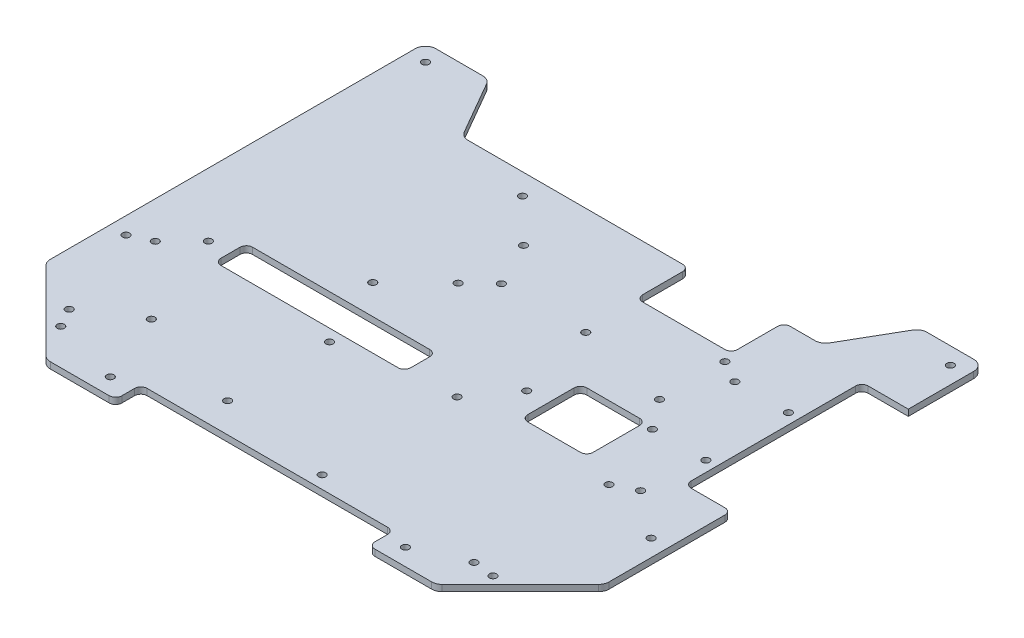
SolidWorks part; units mm, degrees
material "Acier non allié"
ref_plane "Front" through (0, 0, 0) normal (0, 0, 1) x (1, 0, 0)
ref_plane "Top" through (0, 0, 0) normal (0, 1, 0) x (1, 0, 0)
ref_plane "Right" through (0, 0, 0) normal (1, 0, 0) x (0, 0, -1)
sketch "Esquisse1" plane through (0, 0, 0) normal (0, 1, 0) x (1, 0, 0)
  line L0 (0, 0) -> (0, 190) construction
  line L1 (-92.5, 0) -> (92.5, 0)
  line L2 (92.5, 0) -> (132.5, 40)
  line L3 (132.5, 40) -> (132.5, 220)
  line L4 (132.5, 220) -> (102.5, 220)
  line L5 (102.5, 220) -> (85.1795, 190)
  line L6 (85.1795, 190) -> (-85.1795, 190)
  line L7 (-102.5, 220) -> (-85.1795, 190)
  line L8 (-132.5, 220) -> (-102.5, 220)
  line L9 (-132.5, 40) -> (-132.5, 220)
  line L10 (-92.5, 0) -> (-132.5, 40)
  dimension "D1" = 132.5
  dimension "D2" = 220
  dimension "D3" = 60
  dimension "D4" = 30
  dimension "D5" = 40
  dimension "D6" = 40
  dimension "D7" = 30
extrude "Boss.-Extru.1" add sketch "Esquisse1" along normal blind 3
fillet "Congé1" radius 5 10 edges at (92.5, 1.5, 0) (132.5, 1.5, -40) (132.5, 1.5, -220) (102.5, 1.5, -220) (85.1795, 1.5, -190) (-85.1795, 1.5, -190) (-102.5, 1.5, -220) (-132.5, 1.5, -220) (-92.5, 1.5, 0) (-132.5, 1.5, -40)
sketch "Esquisse2" plane through (0, 3, 0) normal (0, 1, 0) x (1, 0, 0)
  line L0 (0, 0) -> (0, 294.1173) construction
  line L2 (-90.4289, 0) -> (90.4289, 0) construction
  circle A0 centre (70, 8) radius 1
  circle A1 centre (124.5, 70) radius 1
  circle A2 centre (124.5, 212) radius 1
  circle A3 centre (-124.5, 212) radius 1
  circle A4 centre (-124.5, 70) radius 1
  circle A5 centre (-70, 8) radius 1
  dimension "D2" = 2
  dimension "D6" = 2
  dimension "D9" = 2
  dimension "D1" = 70
  dimension "D3" = 8
  dimension "D4" = 124.5
  dimension "D5" = 70
  dimension "D7" = 124.5
  dimension "D8" = 212
extrude "Enlèv. mat.-Extru.1" cut sketch "Esquisse2" against normal blind 3
hole_wizard "Dégagement M31" positions "Esquisse3" profile "Esquisse4" hole size "M3" standard "ISO" end condition through all
sketch "Esquisse3" plane through (0, 3, 0) normal (0, 1, 0) x (1, 0, 0)
  point P0 (70, 8)
  point P3 (-70, 8)
  point P6 (-124.5, 70)
  point P9 (-124.5, 212)
  point P12 (124.5, 212)
  point P15 (124.5, 70)
sketch "Esquisse4" plane through (70, 3, -8) normal (1, 0, 0) x (0, 0, 1)
  line L0 (0, 0) -> (0, 3)
  line L1 (0, 3) -> (1.7, 3)
  line L2 (1.7, 3) -> (1.7, 0)
  line L5 (1.7, 0) -> (0, 0)
  line L11 (0, -6.35) -> (0, 107.95) construction
  dimension "Diamètre du perçage jusqu'au prochain" = 3.4
  dimension "Profondeur du perçage jusqu'au prochain" = 3
sketch "Esquisse5" plane through (0, 3, 0) normal (0, 1, 0) x (1, 0, 0)
  line L0 (82.2927, 190) -> (-82.2927, 190) construction
  line L1 (67.5, 190) -> (22.5, 190)
  line L2 (67.5, 190) -> (67.5, 165)
  line L3 (67.5, 165) -> (22.5, 165)
  line L4 (22.5, 190) -> (22.5, 165)
  line L5 (132.5, 42.0711) -> (132.5, 215) construction
  line L6 (132.5, 184) -> (110.5, 184)
  line L7 (132.5, 184) -> (132.5, 100)
  line L8 (132.5, 100) -> (110.5, 100)
  line L9 (110.5, 184) -> (110.5, 100)
  line L10 (127.5, 220) -> (105.3868, 220) construction
  dimension "D1" = 25
  dimension "D2" = 65
  dimension "D3" = 110
  dimension "D4" = 36
  dimension "D5" = 120
  dimension "D6" = 22
extrude "Enlèv. mat.-Extru.2" cut sketch "Esquisse5" against normal through all
fillet "Congé2" radius 3 7 edges at (132.5, 1.5, -100) (110.5, 1.5, -100) (110.5, 1.5, -184) (67.5, 1.5, -190) (67.5, 1.5, -165) (22.5, 1.5, -165) (22.5, 1.5, -190)
sketch "Esquisse6" plane through (0, 3, 0) normal (0, 1, 0) x (1, 0, 0)
  line L0 (110.5, 144.5) -> (-167.6757, 144.5) construction
  line L1 (110.5, 181) -> (110.5, 103) construction
  line L2 (-90.4289, 0) -> (90.4289, 0) construction
  line L3 (110.5, 181) -> (110.5, 103) construction
  circle A0 centre (69.5, 160) radius 1
  circle A1 centre (-26, 160) radius 1
  circle A2 centre (-46.5, 180) radius 1
  circle A3 centre (69.5, 129) radius 1
  circle A4 centre (-26, 129) radius 1
  circle A5 centre (-46.5, 109) radius 1
  dimension "D4" = 2
  dimension "D6" = 2
  dimension "D10" = 2
  dimension "D1" = 144.5
  dimension "D2" = 41
  dimension "D3" = 15.5
  dimension "D5" = 136.5
  dimension "D7" = 15.5
  dimension "D8" = 35.5
  dimension "D9" = 157
extrude "Enlèv. mat.-Extru.3" cut sketch "Esquisse6" against normal through all
hole_wizard "Dégagement M32" positions "Esquisse7" profile "Esquisse8" hole size "M3" standard "ISO"
sketch "Esquisse7" plane through (0, 3, 0) normal (0, 1, 0) x (1, 0, 0)
  point P0 (-46.5, 109)
  point P3 (-26, 129)
  point P6 (-26, 160)
  point P9 (-46.5, 180)
  point P12 (69.5, 160)
  point P15 (69.5, 129)
sketch "Esquisse8" plane through (-46.5, 3, -109) normal (1, 0, 0) x (0, 0, 1)
  line L0 (0, 0) -> (0, 11.0215)
  line L1 (0, 11.0215) -> (1.7, 10)
  line L2 (1.7, 10) -> (1.7, 0)
  line L5 (1.7, 0) -> (0, 0)
  line L10 (0, 11.0215) -> (-1.7, 10) construction
  line L11 (0, -6.35) -> (0, 107.95) construction
  dimension "Diamètre du perçage" = 3.4
  dimension "Profondeur du perçage" = 10
  dimension "Angle de pointe" = 118
sketch "Esquisse9" plane through (0, 3, 0) normal (0, 1, 0) x (1, 0, 0)
  line L0 (132.5, 42.0711) -> (132.5, 97) construction
  line L1 (-90.4289, 0) -> (90.4289, 0) construction
  line L2 (-107.5, 26) -> (-32.37, 26) construction
  line L7 (20.5, 18) -> (20.5, 82) construction
  line L8 (25.5, 165) -> (64.5, 165) construction
  line L9 (24.5, 139) -> (-15.5, 139) construction
  line L10 (110.5, 181) -> (110.5, 103) construction
  line L12 (127.5, 220) -> (105.3868, 220) construction
  line L13 (-32.37, 26) -> (-32.37, 74.3362) construction
  line L14 (-32.37, 74.3362) -> (-115, 74.3362) construction
  line L15 (-132.5, 215) -> (-132.5, 42.0711) construction
  circle A0 centre (105.5, 115) radius 1
  circle A3 centre (105.5, 154.12) radius 1
  circle A10 centre (20.5, 82) radius 1
  circle A11 centre (92.5, 82) radius 1
  circle A12 centre (20.5, 18) radius 1
  circle A13 centre (92.5, 18) radius 1
  circle A14 centre (-15.5, 139) radius 1
  circle A15 centre (24.5, 139) radius 1
  circle A16 centre (34.5, 101) radius 1
  circle A17 centre (80.1, 115) radius 1
  circle A18 centre (80.1, 154.12) radius 1
  circle A19 centre (-107.5, 26) radius 1.5
  circle A21 centre (-32.37, 26) radius 1.5
  circle A22 centre (-32.37, 74.3362) radius 1.5
  circle A23 centre (-115, 74.3362) radius 1.5
  circle A24 centre (-83.99, 41.44) radius 1.5
  dimension "D2" = 2
  dimension "D4" = 2
  dimension "D21" = 2
  dimension "D22" = 2
  dimension "D23" = 2
  dimension "D24" = 2
  dimension "D32" = 2
  dimension "D33" = 2
  dimension "D34" = 2
  dimension "D11" = 2
  dimension "D12" = 2
  dimension "D17" = 3
  dimension "D18" = 3
  dimension "D19" = 3
  dimension "D36" = 3
  dimension "D42" = 3
  dimension "D5" = 27
  dimension "25" = 27
  dimension "D10" = 39.12
  dimension "D25" = 72
  dimension "D26" = 72
  dimension "D27" = 64
  dimension "D28" = 64
  dimension "D30" = 18
  dimension "D31" = 18
  dimension "D37" = 40
  dimension "D39" = 10
  dimension "D8" = 25.4
  dimension "D9" = 25.4
  dimension "D40" = 39.12
  dimension "D38" = 76
  dimension "D6" = 38
  dimension "D35" = 26
  dimension "D14" = 40
  dimension "D13" = 75.13
  dimension "D15" = 82.63
  dimension "D16" = 48.3362
  dimension "D20" = 26
  dimension "D29" = 25
  dimension "D41" = 23.51
  dimension "D43" = 15.44
  dimension "D7" = 105
extrude "Enlèv. mat.-Extru.4" cut sketch "Esquisse9" against normal through all
hole_wizard "Dégagement M33" positions "Esquisse10" profile "Esquisse11" hole size "M3" standard "ISO"
sketch "Esquisse10" plane through (0, 3, 0) normal (0, 1, 0) x (1, 0, 0)
  point P3 (105.5, 115)
  point P9 (105.5, 154.12)
  point P14 (80.1, 154.12)
  point P17 (80.1, 115)
sketch "Esquisse11" plane through (105.5, 3, -115) normal (1, 0, 0) x (0, 0, 1)
  line L0 (0, 0) -> (0, 11.0215)
  line L1 (0, 11.0215) -> (1.7, 10)
  line L2 (1.7, 10) -> (1.7, 0)
  line L5 (1.7, 0) -> (0, 0)
  line L10 (0, 11.0215) -> (-1.7, 10) construction
  line L11 (0, -6.35) -> (0, 107.95) construction
  dimension "Diamètre du perçage" = 3.4
  dimension "Profondeur du perçage" = 10
  dimension "Angle de pointe" = 118
sketch "Esquisse12" plane through (0, 3, 0) normal (0, 1, 0) x (1, 0, 0)
  line L2 (-90.4289, 0) -> (90.4289, 0) construction
  line L3 (102.5, 17) -> (-102.5, 17) construction
  line L4 (102.5, 17) -> (102.5, 87) construction
  line L5 (102.5, 87) -> (-102.5, 87) construction
  line L6 (-102.5, 17) -> (-102.5, 87) construction
  line L7 (132.5, 42.0711) -> (132.5, 97) construction
  circle A4 centre (-102.5, 87) radius 1
  circle A5 centre (102.5, 87) radius 1
  circle A6 centre (102.5, 17) radius 1
  circle A7 centre (-102.5, 17) radius 1
  point P6 (102.5, 52)
  dimension "D5" = 2
  dimension "D6" = 2
  dimension "D7" = 2
  dimension "D8" = 2
  dimension "D1" = 70
  dimension "D2" = 205
  dimension "D3" = 17
  dimension "D4" = 30
extrude "Enlèv. mat.-Extru.5" cut sketch "Esquisse12" against normal through all and the other way through all
hole_wizard "Dégagement M34" positions "Esquisse13" profile "Esquisse14" hole size "M3" standard "ISO"
sketch "Esquisse13" plane through (0, 3, 0) normal (0, 1, 0) x (1, 0, 0)
  point P16 (20.5, 18)
  point P19 (92.5, 18)
  point P22 (20.5, 82)
  point P25 (92.5, 82)
  point P29 (34.5, 101)
  point P32 (24.5, 139)
  point P35 (-15.5, 139)
  point P38 (-115, 74.3362)
  point P41 (-32.37, 74.3362)
  point P44 (-107.5, 26)
  point P47 (-32.37, 26)
  point P50 (-83.99, 41.44)
sketch "Esquisse14" plane through (20.5, 3, -18) normal (1, 0, 0) x (0, 0, 1)
  line L0 (0, 0) -> (0, 11.0215)
  line L1 (0, 11.0215) -> (1.7, 10)
  line L2 (1.7, 10) -> (1.7, 0)
  line L5 (1.7, 0) -> (0, 0)
  line L10 (0, 11.0215) -> (-1.7, 10) construction
  line L11 (0, -6.35) -> (0, 107.95) construction
  dimension "Diamètre du perçage" = 3.4
  dimension "Profondeur du perçage" = 10
  dimension "Angle de pointe" = 118
hole_wizard "Dégagement M35" positions "Esquisse15" profile "Esquisse16" hole size "M3" standard "ISO"
sketch "Esquisse15" plane through (0, 3, 0) normal (0, 1, 0) x (1, 0, 0)
  point P0 (-102.5, 17)
  point P3 (-102.5, 87)
  point P6 (102.5, 87)
  point P9 (102.5, 17)
sketch "Esquisse16" plane through (-102.5, 3, -17) normal (1, 0, 0) x (0, 0, 1)
  line L0 (0, 0) -> (0, 11.0215)
  line L1 (0, 11.0215) -> (1.7, 10)
  line L2 (1.7, 10) -> (1.7, 0)
  line L5 (1.7, 0) -> (0, 0)
  line L10 (0, 11.0215) -> (-1.7, 10) construction
  line L11 (0, -6.35) -> (0, 107.95) construction
  dimension "Diamètre du perçage" = 3.4
  dimension "Profondeur du perçage" = 10
  dimension "Angle de pointe" = 118
sketch "Esquisse17" plane through (0, 3, 0) normal (0, 1, 0) x (1, 0, 0)
  line L0 (-90.4289, 0) -> (90.4289, 0) construction
  line L1 (-92.5, 95) -> (-2.5, 95)
  line L2 (-92.5, 95) -> (-92.5, 80)
  line L3 (-92.5, 80) -> (-2.5, 80)
  line L4 (-2.5, 95) -> (-2.5, 80)
  line L5 (-132.5, 215) -> (-132.5, 42.0711) construction
  line L6 (132.5, 42.0711) -> (132.5, 97) construction
  line L7 (44.5, 116.5) -> (75.5, 116.5)
  line L8 (44.5, 116.5) -> (44.5, 88.5)
  line L9 (44.5, 88.5) -> (75.5, 88.5)
  line L10 (75.5, 116.5) -> (75.5, 88.5)
  line L11 (82.2927, 190) -> (70.5, 190) construction
  line L13 (-59.5, 12) -> (60.5, 12)
  line L14 (-59.5, 12) -> (-59.5, 0)
  line L15 (-59.5, 0) -> (60.5, 0)
  line L16 (60.5, 12) -> (60.5, 0)
  dimension "D1" = 90
  dimension "D2" = 15
  dimension "D3" = 80
  dimension "D4" = 40
  dimension "D5" = 31
  dimension "D6" = 28
  dimension "D7" = 57
  dimension "D8" = 73.5
  dimension "D9" = 12
  dimension "D11" = 120
  dimension "D12" = 72
extrude "Enlèv. mat.-Extru.6" cut sketch "Esquisse17" against normal up to surface (3 mm away) up to face at (-102.5, 0, -15.3)
fillet "Congé3" radius 3 12 edges at (60.5, 1.5, 0) (60.5, 1.5, -12) (-59.5, 1.5, -12) (-59.5, 1.5, 0) (44.5, 1.5, -116.5) (75.5, 1.5, -116.5) (75.5, 1.5, -88.5) (44.5, 1.5, -88.5) (-92.5, 1.5, -80) (-2.5, 1.5, -80) (-2.5, 1.5, -95) (-92.5, 1.5, -95)
equation "\"WIDTH\"= 300mm'Total width of the robot"
equation "\"LENGTH\"= 220mm'Total length of the robot"
equation "\"CUT_DEPTH\"= 45mm'Depth of the cut on the edges of the plate"
equation "\"Plate_th\"= 3mm'Thickness of the plate"
equation "\"D1\"= \"Plate_th\""
equation "\"D5@Esquisse9\"=\"25@Esquisse9\""
